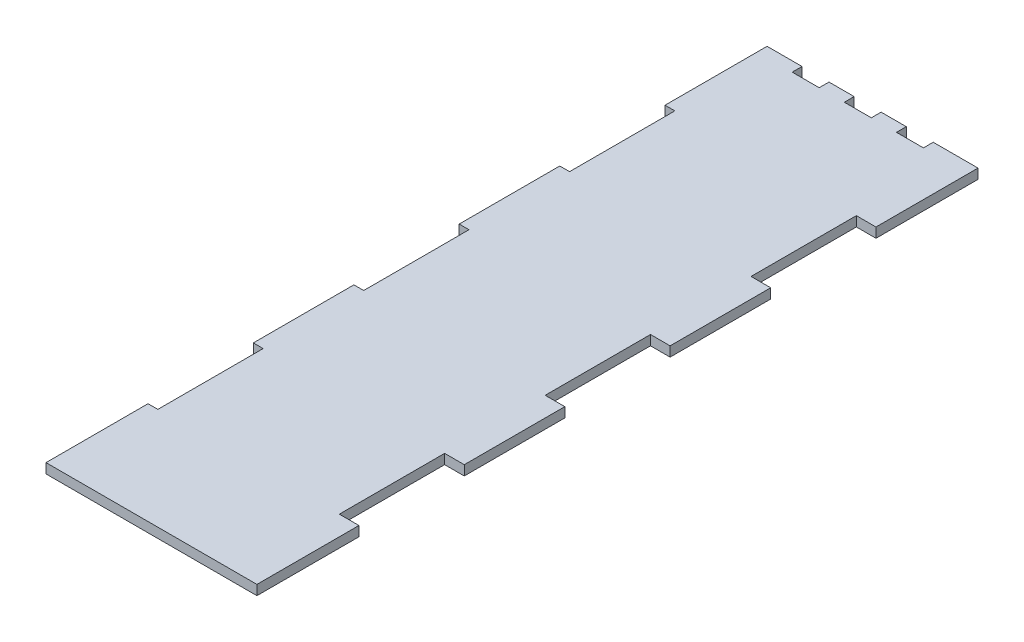
SolidWorks part; units mm, degrees
ref_plane "前视基准面" through (0, 0, 0) normal (0, 0, 1) x (1, 0, 0)
ref_plane "上视基准面" through (0, 0, 0) normal (0, 1, 0) x (1, 0, 0)
ref_plane "右视基准面" through (0, 0, 0) normal (1, 0, 0) x (0, 0, -1)
other "Configuration Table"
sketch "草图4" plane through (0, 0, 0) normal (0, 1, 0) x (1, 0, 0)
  line L6 (-18.5, -72.5) -> (18.5, -72.5)
  line L11 (-18.5, -72.5) -> (-18.5, 72.5)
  line L12 (-18.5, 72.5) -> (18.5, 72.5)
  line L13 (18.5, -72.5) -> (18.5, 72.5)
  line L14 (-18.5, -72.5) -> (18.5, 72.5) construction
  line L15 (-18.5, 72.5) -> (18.5, -72.5) construction
  point P0 (0, 0)
  dimension "D1" = 37
  dimension "D2" = 145
extrude "凸台-拉伸1" add sketch "草图4" along normal blind 2
sketch "草图5" plane through (0, 0, -72.5) normal (0, 0, -1) x (-1, 0, 0)
  line L0 (-18.5, 2) -> (18.5, 2) construction
  line L1 (18.5, 0) -> (13.375, 0)
  line L2 (18.5, 0) -> (18.5, 2)
  line L3 (18.5, 2) -> (13.375, 2)
  line L4 (13.375, 0) -> (13.375, 2)
  line L5 (-18.5, 0) -> (18.5, 0) construction
  line L6 (7.875, 0) -> (2.75, 0)
  line L7 (7.875, 0) -> (7.875, 2)
  line L8 (7.875, 2) -> (2.75, 2)
  line L9 (2.75, 0) -> (2.75, 2)
  line L10 (13.375, 0) -> (7.875, 0)
  line L11 (-2.75, 0) -> (-7.875, 0)
  line L12 (-2.75, 0) -> (-2.75, 2)
  line L13 (-2.75, 2) -> (-7.875, 2)
  line L14 (-7.875, 0) -> (-7.875, 2)
  line L15 (-13.375, 0) -> (-18.5, 0)
  line L16 (-13.375, 0) -> (-13.375, 2)
  line L17 (-13.375, 2) -> (-18.5, 2)
  line L18 (-18.5, 0) -> (-18.5, 2)
  line L19 (2.75, 0) -> (-2.75, 0)
  line L20 (-7.875, 0) -> (-13.375, 0)
  line M17 (-18.5, 0) -> (18.5, 0)
  line M18 (18.5, 0) -> (18.5, 2)
  line M19 (18.5, 2) -> (-18.5, 2)
  line M20 (-18.5, 2) -> (-18.5, 0)
  dimension "D1" = 5.5
extrude "凸台-拉伸2" add sketch "草图5" along normal blind 2 contours L16 M17 M19 M20 | L14 L12 M17 M19 | L9 L7 M17 M19 | L4 M17 M18 M19 region at (-15.9375, 1, -72.5) region at (-5.3125, 1, -72.5) region at (5.3125, 1, -72.5) region at (15.9375, 1, -72.5)
sketch "草图7" plane through (18.5, 0, 0) normal (1, 0, 0) x (0, 0, -1)
  line L0 (-72.5, 2) -> (74.5, 2) construction
  line L1 (-72.5, 0) -> (-51.7, 0)
  line L2 (-72.5, 0) -> (-72.5, 2)
  line L3 (-72.5, 2) -> (-51.7, 2)
  line L4 (-51.7, 0) -> (-51.7, 2)
  line L5 (-72.5, 0) -> (74.5, 0) construction
  line L6 (-30.2333, 0) -> (-9.7333, 0)
  line L7 (-30.2333, 0) -> (-30.2333, 2)
  line L8 (-30.2333, 2) -> (-9.7333, 2)
  line L9 (-9.7333, 0) -> (-9.7333, 2)
  line L10 (-51.7, 1) -> (-30.2333, 1) construction
  line L11 (11.7333, 0) -> (32.2333, 0)
  line L12 (11.7333, 0) -> (11.7333, 2)
  line L13 (11.7333, 2) -> (32.2333, 2)
  line L14 (32.2333, 0) -> (32.2333, 2)
  line L15 (53.7, 0) -> (74.5, 0)
  line L16 (53.7, 0) -> (53.7, 2)
  line L17 (53.7, 2) -> (74.5, 2)
  line L18 (74.5, 0) -> (74.5, 2)
  line L19 (-9.7333, 1) -> (11.7333, 1) construction
  line L20 (32.2333, 1) -> (53.7, 1) construction
  dimension "D1" = 20.8
  dimension "D2" = 20.5
extrude "凸台-拉伸3" add sketch "草图7" along normal blind 4
extrude "凸台-拉伸4" add sketch "草图7<2>" against normal blind 2 from surface starting at face at (-18.5, 1, -1)
sketch "草图7<2>" plane through (18.5, 0, 0) normal (1, 0, 0) x (0, 0, -1) same geometry as "草图7"
sketch "草图9" plane through (0, 0, 72.5) normal (0, 0, 1) x (1, 0, 0)
  line L0 (-9.8, 0) -> (-11.6, -1.8)
  line L1 (-11.6, -1.8) -> (-9.8, -1.8)
  line L2 (-9.8, -1.8) -> (9.8, -1.8)
  line L3 (9.8, -1.8) -> (11.6, -1.8)
  line L4 (11.6, -1.8) -> (9.8, 0)
  line L5 (-20.5, 0) -> (22.5, 0) construction
  line L6 (9.8, 0) -> (9.8, -1.8) construction
  line L7 (-9.8, -1.8) -> (-9.8, 0) construction
  line L8 (-9.8, 0) -> (9.8, 0)
  line L9 (0, 0) -> (0, -1.8) construction
  dimension "D1" = 1.8
  dimension "D2" = 19.6
extrude "凸台-拉伸5" add sketch "草图9" against normal up to surface (145 mm away) from offset 2.2 up to face at (0, 1, -72.5) offset against normal yes
